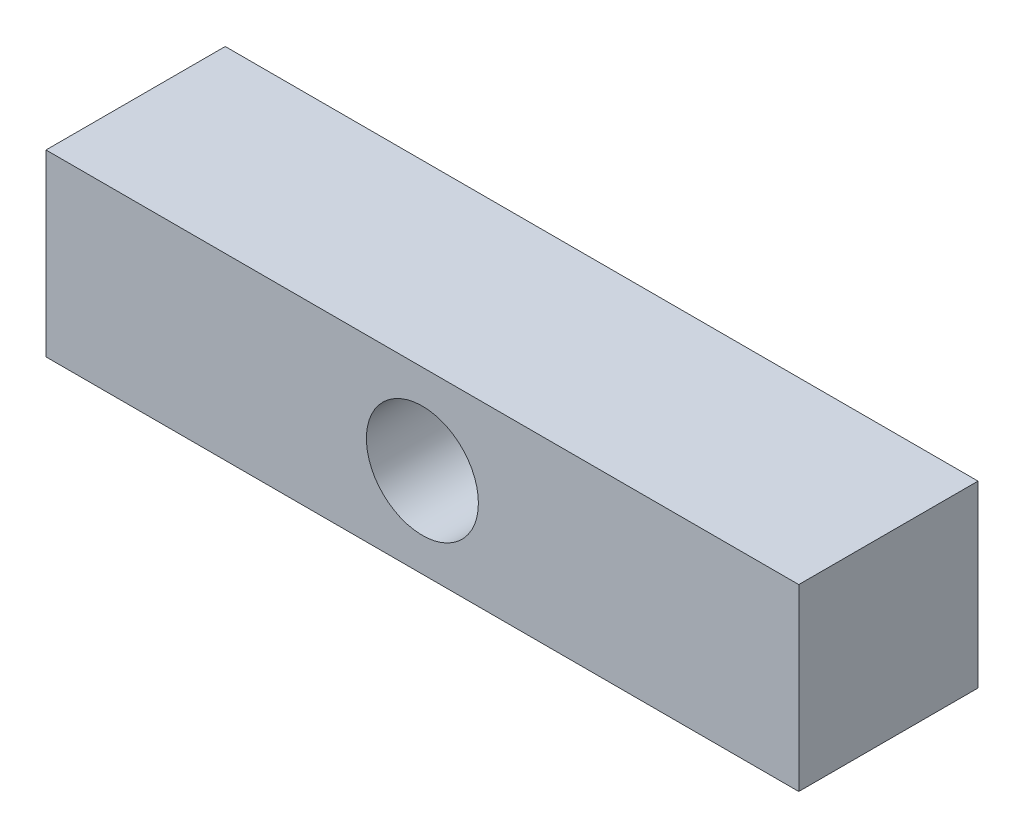
SolidWorks part; units mm, degrees
material "ABS"
ref_plane "Front Plane" through (0, 0, 0) normal (0, 0, 1) x (1, 0, 0)
ref_plane "Top Plane" through (0, 0, 0) normal (0, 1, 0) x (1, 0, 0)
ref_plane "Right Plane" through (0, 0, 0) normal (1, 0, 0) x (0, 0, -1)
sketch "Sketch1" plane through (0, 0, 0) normal (0, 0, 1) x (1, 0, 0)
  line L0 (38.1, 0) -> (-38.1, 0) construction
  line L1 (53.34, 12.7) -> (-53.34, 12.7)
  line L2 (53.34, 12.7) -> (53.34, -12.7)
  line L3 (53.34, -12.7) -> (-53.34, -12.7)
  line L4 (-53.34, 12.7) -> (-53.34, -12.7)
  line L5 (53.34, 12.7) -> (-53.34, -12.7) construction
  line L6 (53.34, -12.7) -> (-53.34, 12.7) construction
  circle A0 centre (38.1, 0) radius 8.1915
  circle A1 centre (-38.1, 0) radius 8.1915
  point P0 (0, 0)
  point P10 (0, 0)
  dimension "D1" = 16.383
  dimension "D2" = 76.2
  dimension "D3" = 15.24
  dimension "D4" = 12.7
extrude "Boss-Extrude1" add sketch "Sketch1" along normal blind 25.4 contours L3 L4 L1 L2
extrude "Cut-Extrude1" cut sketch "Sketch1<3>" along normal blind 19.05 contours A1 | A0 region at (-38.1, 0, 0)
sketch "Sketch1<3>" plane through (0, 0, 0) normal (0, 0, 1) x (1, 0, 0) same geometry as "Sketch1"
hole_wizard "CBORE for 1/4 Binding Head Machine Screw1" positions "Sketch2" profile "Sketch3" counterbore size "1/4" standard "ANSI Inch" end condition up to next
sketch "Sketch2" plane through (0, 0, 25.4) normal (0, 0, 1) x (1, 0, 0)
  point P0 (0, 0)
sketch "Sketch3" plane through (0, 0, 25.4) normal (1, 0, 0) x (0, -1, 0)
  line L0 (0, 0) -> (0, 25.4)
  line L1 (0, 25.4) -> (4.0132, 25.4)
  line L3 (4.0132, 25.4) -> (4.0132, 19.05)
  line L4 (4.0132, 19.05) -> (7.9375, 19.05)
  line L5 (7.9375, 19.05) -> (7.9375, 0)
  line L7 (7.9375, 0) -> (0, 0)
  line L11 (0, -6.35) -> (0, 107.95) construction
  dimension "Thru Hole Dia." = 8.0264
  dimension "Thru Hole Depth" = 25.4
  dimension "C'Bore Dia." = 15.875
  dimension "C'Bore Depth" = 19.05
